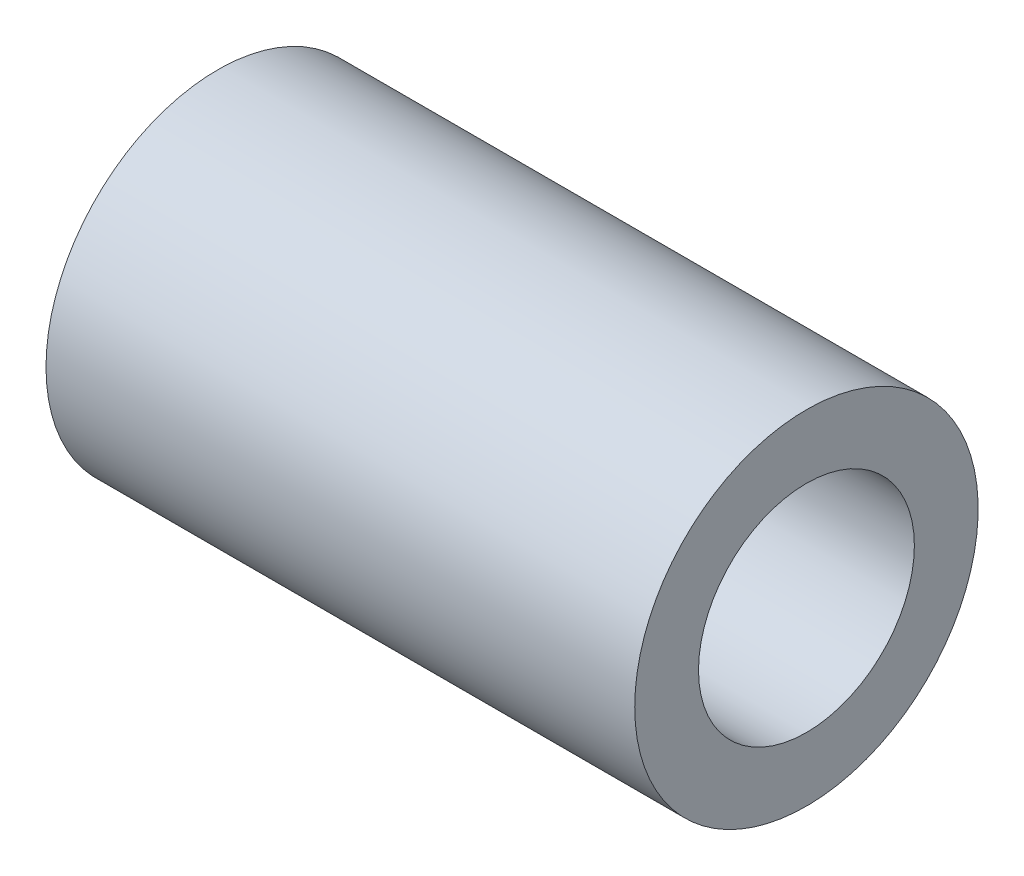
SolidWorks part; units mm, degrees
ref_plane "Front Plane" through (0, 0, 0) normal (0, 0, 1) x (1, 0, 0)
ref_plane "Top Plane" through (0, 0, 0) normal (0, 1, 0) x (1, 0, 0)
ref_plane "Right Plane" through (0, 0, 0) normal (1, 0, 0) x (0, 0, -1)
sketch "Sketch1" plane through (0, 0, 0) normal (1, 0, 0) x (0, 0, -1)
  circle A0 centre (0, 0) radius 2.794
  circle A1 centre (0, 0) radius 4.445
  dimension "D1" = 5.588
  dimension "D2" = 8.89
extrude "Boss-Extrude1" add sketch "Sketch1" along normal blind 15.24 contours A1 A0 region at (0, 0, 4.3193)
